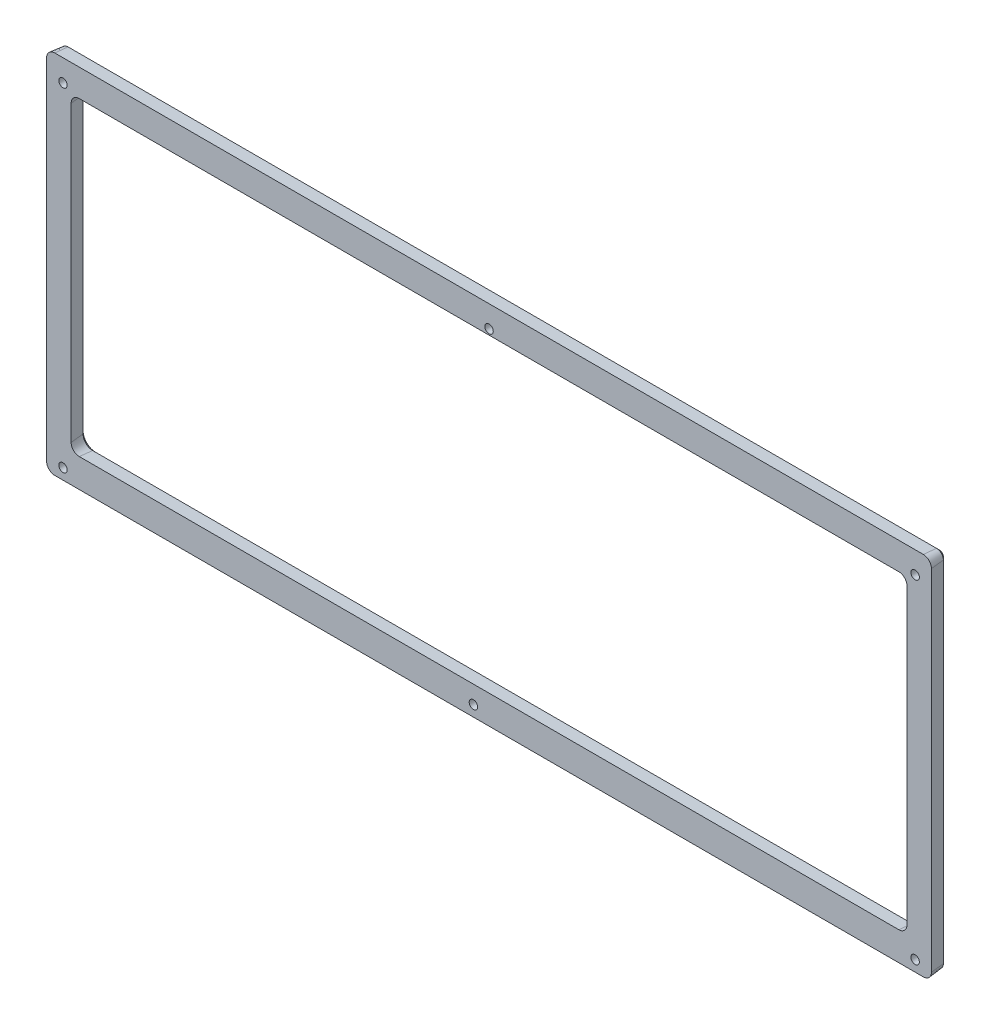
SolidWorks part; units mm, degrees
note: The reader was unsure of these and kept them because the rebuilt part matched: shared geometry of "草图3<3>".
ref_plane "前视基准面" through (0, 0, 0) normal (0, 0, 1) x (1, 0, 0)
ref_plane "上视基准面" through (0, 0, 0) normal (0, 1, 0) x (1, 0, 0)
ref_plane "右视基准面" through (0, 0, 0) normal (1, 0, 0) x (0, 0, -1)
sketch "草图3" plane through (0, 0, 0) normal (0, 0, 1) x (1, 0, 0)
  line L0 (-9.9049, 123.558) -> (-9.9049, -4.7423)
  line L1 (311.8951, 126.558) -> (-6.9049, 126.558)
  line L2 (314.8951, -4.7423) -> (314.8951, 123.558)
  line L3 (-6.9049, -7.7423) -> (311.8951, -7.7423)
  line L5 (2.0951, 116.558) -> (302.8951, 116.558)
  line L6 (-0.9049, 113.558) -> (-0.9049, 5.7577)
  line L7 (2.0951, 2.7577) -> (302.8951, 2.7577)
  line L8 (305.8951, 113.558) -> (305.8951, 5.7577)
  arc A0 (-0.9049, 5.7577) -> (2.0951, 2.7577) centre (2.0951, 5.7577) ccw
  arc A1 (302.8951, 2.7577) -> (305.8951, 5.7577) centre (302.8951, 5.7577) ccw
  arc A2 (305.8951, 113.558) -> (302.8951, 116.558) centre (302.8951, 113.558) ccw
  arc A3 (-0.9049, 113.558) -> (2.0951, 116.558) centre (2.0951, 113.558) cw
  circle A4 centre (-3.9049, 118.558) radius 1.55
  circle A5 centre (308.896, -3.7423) radius 1.55
  circle A6 centre (146.756, -3.7423) radius 1.55
  circle A7 centre (-3.9049, -3.7423) radius 1.55
  circle A8 centre (308.896, 118.558) radius 1.55
  circle A9 centre (152.4955, 118.558) radius 1.55
  arc A10 (-9.9049, 123.558) -> (-6.9049, 126.558) centre (-6.9049, 123.558) cw
  arc A11 (-6.9049, -7.7423) -> (-9.9049, -4.7423) centre (-6.9049, -4.7423) cw
  arc A12 (311.8951, -7.7423) -> (314.8951, -4.7423) centre (311.8951, -4.7423) ccw
  arc A13 (314.8951, 123.558) -> (311.8951, 126.558) centre (311.8951, 123.558) ccw
  point P0 (0, 0.001)
  point P1 (0.001, 0.001)
  point P2 (0.001, 0)
  dimension "D1" = 107.8003
  dimension "D3" = 10
  dimension "D7" = 3
  dimension "D8" = 162.14
  dimension "D9" = 3
  dimension "D10" = 3
  dimension "D2" = 300.8
  dimension "D4" = 9
  dimension "D5" = 9
  dimension "D6" = 10.5
extrude "凸台-拉伸1" add sketch "草图3" against normal blind 6 draft 6 contours L3 A12 L2 A13 L1 A10 L0 A11 | L7 A1 L8 A2 L5 A3 L6 A0
chamfer "倒角2" distance 1 angle 45 8 edges at (305.4623, 3.1905, -6) (152.4951, 2.1271, -6) (-0.4722, 3.1905, -6) (-1.5355, 59.6578, -6) (-0.4722, 116.1252, -6) (152.4951, 117.1886, -6) (305.4623, 116.1252, -6) (306.5257, 59.6578, -6)
extrude "切除-拉伸1" cut sketch "草图3<3>" against normal blind 3.5 contours A7 | A4 | A9 | A8 | A5 | A6
sketch "草图3<3>" plane through (0, 0, 0) normal (0, 0, 1) x (1, 0, 0) same geometry as "草图3"
chamfer "倒角3" distance 1 angle 45 8 edges at (-8.5803, 125.2334, -6) (-9.2743, 59.4078, -6) (-8.5803, -6.4177, -6) (152.4951, -7.1117, -6) (313.5705, -6.4177, -6) (314.2645, 59.4078, -6) (313.5705, 125.2334, -6) (152.4951, 125.9274, -6)
